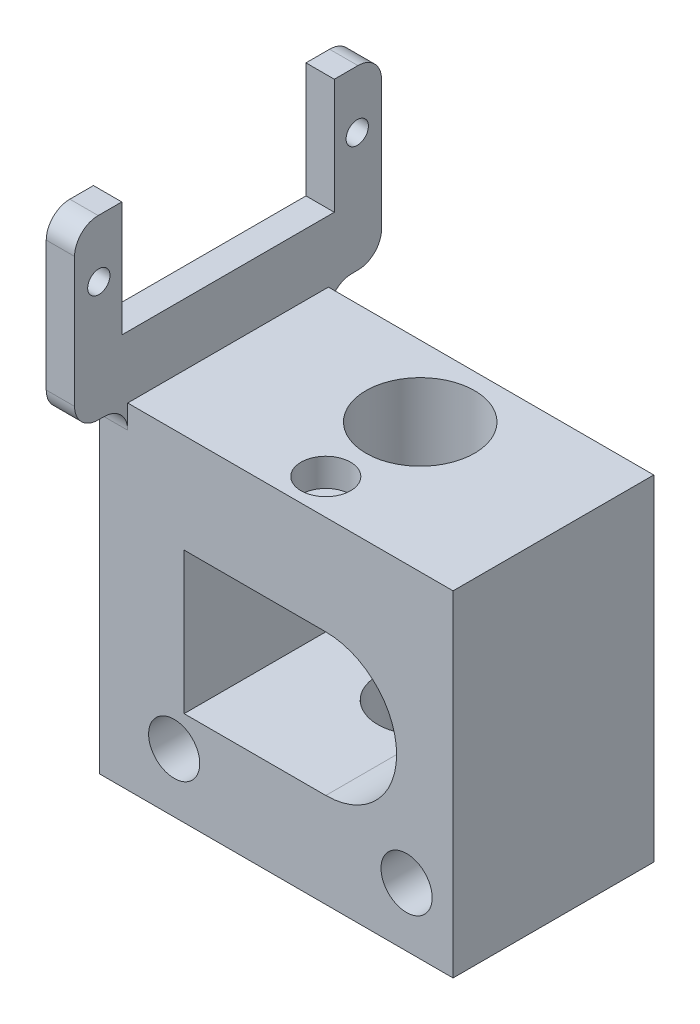
SolidWorks part; units mm, degrees
ref_plane "Front Plane" through (0, 0, 0) normal (0, 0, 1) x (1, 0, 0)
ref_plane "Top Plane" through (0, 0, 0) normal (0, 1, 0) x (1, 0, 0)
ref_plane "Right Plane" through (0, 0, 0) normal (1, 0, 0) x (0, 0, -1)
sketch "Sketch2" plane through (0, 0, 0) normal (0, 0, 1) x (1, 0, 0)
  line L1 (0, 0) -> (35, 0)
  line L2 (0, 0) -> (0, 36.068)
  line L3 (0, 36.068) -> (35, 36.068)
  line L4 (35, 0) -> (35, 36.068)
  dimension "D1" = 36.068
  dimension "D2" = 35
extrude "Boss-Extrude1" add sketch "Sketch2" along normal blind 21.59
hole_wizard "M5 Clearance Hole1" positions "Sketch3" profile "Sketch4" hole size "M5" standard "ANSI Metric" end condition through all
sketch "Sketch3" plane through (0, 0, 0) normal (0, 0, 1) x (1, 0, 0)
  line L0 (5, 6.35) -> (30, 6.35) construction
  line L2 (0, 0) -> (35, 0) construction
  point P0 (5, 6.35)
  point P2 (30, 6.35)
  point P12 (17.5, 0)
  point P13 (17.5, 6.35)
  dimension "D1" = 6.35
  dimension "D2" = 25
sketch "Sketch4" plane through (5, 6.35, 0) normal (1, 0, 0) x (0, 1, 0)
  line L0 (0, 0) -> (0, 21.59)
  line L1 (0, 21.59) -> (2.75, 21.59)
  line L2 (2.75, 21.59) -> (2.75, 0)
  line L5 (2.75, 0) -> (0, 0)
  line L11 (0, -6.35) -> (0, 107.95) construction
  dimension "Thru Hole Dia." = 5.5
  dimension "Thru Hole Depth" = 21.59
sketch "Sketch13" plane through (0, 0, 21.59) normal (0, 0, 1) x (1, 0, 0)
  line L1 (6.07, 25.4) -> (28.93, 25.4)
  line L2 (6.07, 25.4) -> (6.07, 10.16)
  line L3 (6.07, 10.16) -> (28.93, 10.16)
  line L4 (28.93, 25.4) -> (28.93, 10.16)
  line L5 (35, 36.068) -> (0, 36.068) construction
  line L7 (0, 0) -> (35, 0) construction
  point P6 (17.5, 36.068)
  point P7 (17.5, 25.4)
  dimension "D1" = 10.16
  dimension "D2" = 15.24
  dimension "D3" = 22.86
extrude "Cut-Extrude3" cut sketch "Sketch13" against normal through all
sketch "Sketch5" plane through (0, 36.068, 0) normal (0, 1, 0) x (1, 0, 0)
  line L0 (35, 0) -> (0, 0) construction
  circle A0 centre (17.5, -7.62) radius 5.842
  point P6 (17.5, 0)
  point P7 (17.5, -7.3067)
  dimension "D1" = 11.684
  dimension "D2" = 7.62
extrude "Cut-Extrude1" cut sketch "Sketch5" against normal up to next
sketch "Sketch7" plane through (0, 0, 0) normal (-1, 0, 0) x (0, 0, 1)
  line L0 (21.59, 36.068) -> (0, 36.068) construction
  line L5 (-5.715, 36.068) -> (27.305, 36.068)
  line L6 (-5.715, 36.068) -> (-5.715, 55.118)
  line L7 (-5.715, 55.118) -> (27.305, 55.118)
  line L8 (27.305, 36.068) -> (27.305, 55.118)
  line L9 (21.59, 0) -> (0, 0) construction
  line L10 (-3.1039, 48.9204) -> (24.6939, 48.9204) construction
  line L12 (0, 36.068) -> (21.59, 36.068)
  line L13 (0, 36.068) -> (0, 0)
  line L14 (0, 0) -> (21.59, 0)
  line L15 (21.59, 36.068) -> (21.59, 0)
  line L16 (-0.635, 55.118) -> (22.225, 55.118)
  line L17 (-0.635, 55.118) -> (-0.635, 42.7228)
  line L18 (-0.635, 42.7228) -> (22.225, 42.7228)
  line L19 (22.225, 55.118) -> (22.225, 42.7228)
  point P7 (10.795, 55.118)
  point P10 (10.795, 0)
  point P15 (10.795, 48.9204)
  point P16 (10.795, 36.068)
  point P26 (10.795, 42.7228)
  point P27 (0, 0)
  point P28 (22.225, 48.9204)
  dimension "D1" = 33.02
  dimension "D2" = 19.05
  dimension "D3" = 27.7978
  dimension "D4" = 12.3952
  dimension "D5" = 22.86
extrude "Boss-Extrude2" add sketch "Sketch7" along normal blind 3.048
hole_wizard "M2 Clearance Hole1" positions "Sketch9" profile "Sketch10" hole size "M2" standard "ANSI Metric" end condition through all
sketch "Sketch9" plane through (-3.048, 0, 0) normal (-1, 0, 0) x (0, 0, 1)
  point P0 (-3.1039, 48.9204)
  point P3 (24.6939, 48.9204)
sketch "Sketch10" plane through (-3.048, 48.9204, -3.1039) normal (0, 1, 0) x (0, 0, 1)
  line L0 (0, 0) -> (0, 38.048)
  line L1 (0, 38.048) -> (1.2, 38.048)
  line L2 (1.2, 38.048) -> (1.2, 0)
  line L5 (1.2, 0) -> (0, 0)
  line L11 (0, -6.35) -> (0, 107.95) construction
  dimension "Thru Hole Dia." = 2.4
  dimension "Thru Hole Depth" = 38.048
fillet "Fillet2" radius 2.54 6 edges at (-1.524, 36.068, -5.715) (-1.524, 55.118, -5.715) (-1.524, 55.118, 27.305) (-1.524, 36.068, 27.305) (-1.524, 36.068, 0) (-1.524, 36.068, 21.59)
sketch "Sketch11" plane through (0, 36.068, 0) normal (0, 1, 0) x (1, 0, 0)
  line L1 (35, -21.59) -> (0, -21.59) construction
  circle A0 centre (17.5, -17.78) radius 2.667
  point P2 (0, 0)
  point P3 (25.553, -15.4258)
  point P4 (17.7649, -16.51)
  point P5 (17.5, -21.59)
  dimension "D1" = 5.334
  dimension "D3" = 3.81
extrude "Cut-Extrude2" cut sketch "Sketch11" against normal blind 3
sketch "Sketch14" plane through (0, 10.16, 0) normal (0, 1, 0) x (1, 0, 0)
  circle A0 centre (17.5, -7.62) radius 5.842 construction
  circle A1 centre (17.5, -7.62) radius 5.842
  circle A2 centre (17.5, -7.62) radius 4.572
  dimension "D1" = 9.144
extrude "Cut-Extrude4" cut sketch "Sketch14" against normal through all contours A2
fillet "Fillet3" radius 7.62 4 edges at (28.93, 17.78, 0) (28.93, 25.4, 10.795) (28.93, 10.16, 10.795) (28.93, 17.78, 21.59)
equation "\"press fit\"= 0.25mm"
equation "\"wall thick\"= 2mm"
equation "\"marker diamiter\"= 0.44"
equation "\"D1@Sketch5\"=\"marker diamiter\"+2*\"press fit\""
equation "\"D1@Boss-Extrude2\"=\"wall thick\"*1.5"
equation "\"D5@Sketch7\"=0.8858+\"press fit\""
equation "\"pin diamiter\"= 5mm"
equation "\"D1@Sketch11\"=\"pin diamiter\"+\"press fit\""
equation "\"D1@Sketch14\"=\"press fit\"+0.35"
